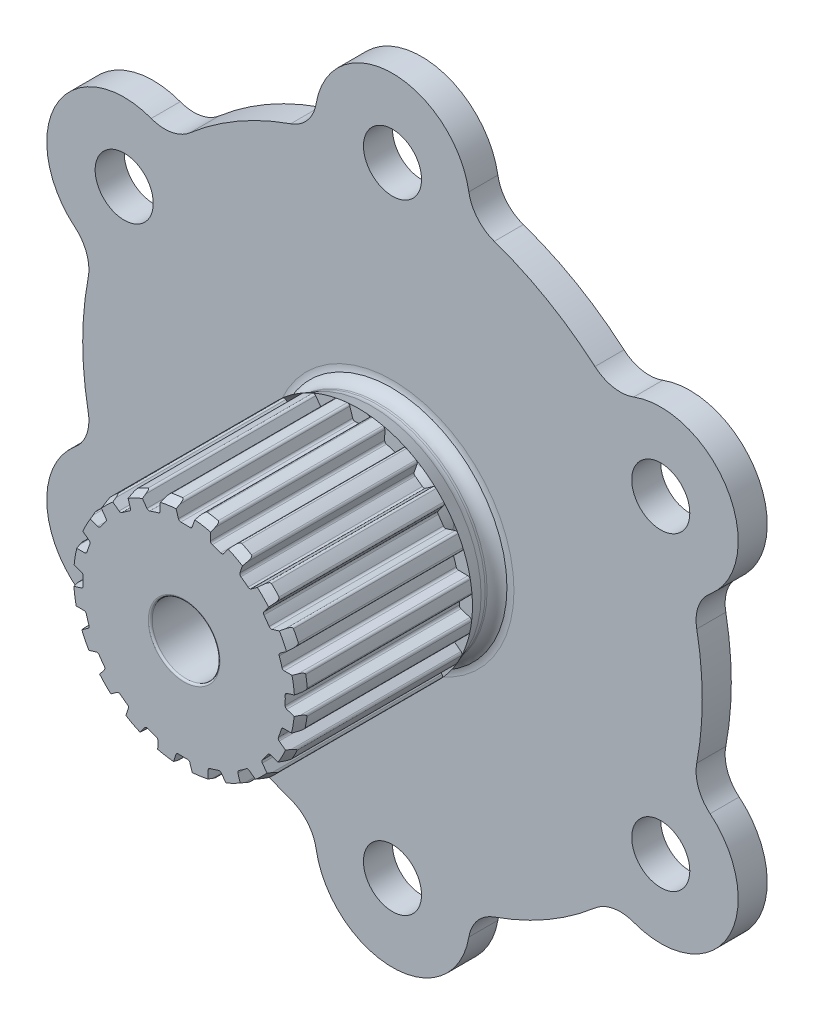
SolidWorks part; units mm, degrees
material "Alloy Steel (SS)"
ref_plane "Front Plane" through (0, 0, 0) normal (0, 0, 1) x (1, 0, 0)
ref_plane "Top Plane" through (0, 0, 0) normal (0, 1, 0) x (1, 0, 0)
ref_plane "Right Plane" through (0, 0, 0) normal (1, 0, 0) x (0, 0, -1)
sketch "Sketch1" plane through (0, 0, 0) normal (0, 0, 1) x (1, 0, 0)
  line L0 (0, -55) -> (0, 55) construction
  line L1 (0, 40) -> (0, 0) construction
  line L2 (0, 0) -> (0, -40) construction
  circle A1 centre (0, 32) radius 3
  circle A2 centre (0, 0) radius 41.3
  circle A3 centre (27.7128, 16) radius 3
  circle A4 centre (0, 0) radius 41.3
  circle A5 centre (27.7128, -16) radius 3
  circle A6 centre (0, 0) radius 41.3
  circle A7 centre (0, -32) radius 3
  circle A8 centre (0, 0) radius 41.3
  circle A9 centre (-27.7128, -16) radius 3
  circle A10 centre (0, 0) radius 41.3
  circle A11 centre (-27.7128, 16) radius 3
  arc A12 (-7.9373, 31) -> (-22.8782, 22.3739) centre (0, 0) ccw
  arc A13 (7.9373, 31) -> (-7.9373, 31) centre (0, 32) ccw
  arc A14 (30.8154, 8.6261) -> (22.8782, 22.3739) centre (27.7128, 16) ccw
  arc A15 (22.8782, -22.3739) -> (30.8154, -8.6261) centre (27.7128, -16) ccw
  arc A16 (-7.9373, -31) -> (7.9373, -31) centre (0, -32) ccw
  arc A17 (-30.8154, -8.6261) -> (-22.8782, -22.3739) centre (-27.7128, -16) ccw
  arc A18 (-22.8782, 22.3739) -> (-30.8154, 8.6261) centre (-27.7128, 16) ccw
  circle A19 centre (0, 32) radius 8 construction
  arc A20 (-22.8782, -22.3739) -> (-7.9373, -31) centre (0, 0) ccw
  arc A21 (30.8154, -8.6261) -> (30.8154, 8.6261) centre (0, 0) ccw
  arc A22 (-30.8154, 8.6261) -> (-30.8154, -8.6261) centre (0, 0) ccw
  arc A23 (7.9373, -31) -> (22.8782, -22.3739) centre (0, 0) ccw
  arc A25 (22.8782, 22.3739) -> (7.9373, 31) centre (0, 0) ccw
  point P25 (0, 0)
  point P38 (0, 0)
  dimension "D1" = 32
  dimension "D5" = 6
  dimension "D6" = 64
  dimension "D3" = 5
  dimension "D2" = 6
  dimension "D4" = 6
extrude "Boss-Extrude1" add sketch "Sketch1" along normal blind 3 contours A11 A9 A7 A5 A3 A1 region at (0, 0, 0)
fillet "Fillet3" radius 4 12 edges at (22.8782, -22.3739, 1.5) (7.9373, -31, 1.5) (-7.9373, -31, 1.5) (-22.8782, -22.3739, 1.5) (-30.8154, -8.6261, 1.5) (-30.8154, 8.6261, 1.5) (-22.8782, 22.3739, 1.5) (-7.9373, 31, 1.5) (7.9373, 31, 1.5) (30.8154, -8.6261, 1.5) (30.8154, 8.6261, 1.5) (22.8782, 22.3739, 1.5)
sketch "Sketch13" plane through (0, 0, 0) normal (0, 0, -1) x (-1, 0, 0)
  circle A0 centre (0, 0) radius 23.95
  circle A1 centre (0, 0) radius 20.95
  dimension "D2" = 47.9
  dimension "D1" = 3
extrude "Boss-Extrude8" add sketch "Sketch13" along normal blind 4
chamfer "Chamfer4" distance 1 angle 45 1 edges at (-23.95, 0, -4)
sketch "Sketch22" plane through (0, 0, 0) normal (1, 0, 0) x (0, 0, -1)
  line L0 (-3, 6.0027) -> (-3, -6.0027) construction
  line L4 (-6.5216, 0) -> (-6.5216, 11.78)
  line L5 (-3, 0) -> (-3, 12.0997)
  line L9 (-6.5216, 11.78) -> (-5.1121, 11.267)
  line L10 (-4.599, 11.1765) -> (-4.399, 11.1765)
  line L11 (-3.1, 11.9265) -> (-3, 12.0997)
  line L13 (-6.5216, 0) -> (-3, 0)
  arc A0 (-3.1, 11.9265) -> (-4.399, 11.1765) centre (-4.399, 12.6765) cw
  arc A1 (-4.599, 11.1765) -> (-5.1121, 11.267) centre (-4.599, 12.6765) cw
  point P0 (-3, 0)
  dimension "D3" = 1.5
  dimension "D1" = 160
  dimension "D2" = 120
  dimension "D4" = 0.2
  dimension "D5" = 1.5
  dimension "D6" = 11.78
  dimension "D7" = 0.2
revolve "Revolve1" add sketch "Sketch22" angle 360 about L13 region at (0, 5.7141, 4.7627)
sketch "Sketch23" plane through (0, 0, 6.5216) normal (0, 0, 1) x (1, 0, 0)
  line L80 (1.152, 11.5221) -> (0.841, 10.6016)
  line L81 (2.7177, 10.2818) -> (2.7291, 11.2534)
  line L82 (4.6562, 10.6022) -> (4.0759, 9.8228)
  line L83 (5.7619, 8.9387) -> (6.073, 9.8593)
  line L84 (7.7045, 8.6444) -> (6.9118, 8.0825)
  line L85 (8.2421, 6.7207) -> (8.8224, 7.5001)
  line L86 (9.9987, 5.8405) -> (9.0712, 5.5511)
  line L87 (9.9156, 3.8448) -> (10.7083, 4.4067)
  line L88 (11.3142, 2.4649) -> (10.3426, 2.4762)
  line L89 (10.6184, 0.5926) -> (11.5459, 0.882)
  line L90 (11.5221, -1.152) -> (10.6016, -0.841)
  line L91 (10.2818, -2.7177) -> (11.2534, -2.7291)
  line L92 (10.6022, -4.6562) -> (9.8228, -4.0759)
  line L93 (8.9387, -5.7619) -> (9.8593, -6.073)
  line L94 (8.6444, -7.7045) -> (8.0825, -6.9118)
  line L95 (6.7207, -8.2421) -> (7.5001, -8.8224)
  line L96 (5.8405, -9.9987) -> (5.5511, -9.0712)
  line L97 (3.8448, -9.9156) -> (4.4067, -10.7083)
  line L98 (2.4649, -11.3142) -> (2.4762, -10.3426)
  line L99 (0.5926, -10.6184) -> (0.882, -11.5459)
  line L100 (-1.152, -11.5221) -> (-0.841, -10.6016)
  line L101 (-2.7177, -10.2818) -> (-2.7291, -11.2534)
  line L102 (-4.6562, -10.6022) -> (-4.0759, -9.8228)
  line L103 (-5.7619, -8.9387) -> (-6.073, -9.8593)
  line L104 (-7.7045, -8.6444) -> (-6.9118, -8.0825)
  line L105 (-8.2421, -6.7207) -> (-8.8224, -7.5001)
  line L106 (-9.9987, -5.8405) -> (-9.0712, -5.5511)
  line L107 (-9.9156, -3.8448) -> (-10.7083, -4.4067)
  line L108 (-11.3142, -2.4649) -> (-10.3426, -2.4762)
  line L109 (-10.6184, -0.5926) -> (-11.5459, -0.882)
  line L110 (-11.5221, 1.152) -> (-10.6016, 0.841)
  line L111 (-10.2818, 2.7177) -> (-11.2534, 2.7291)
  line L112 (-10.6022, 4.6562) -> (-9.8228, 4.0759)
  line L113 (-8.9387, 5.7619) -> (-9.8593, 6.073)
  line L114 (-8.6444, 7.7045) -> (-8.0825, 6.9118)
  line L115 (-6.7207, 8.2421) -> (-7.5001, 8.8224)
  line L116 (-5.8405, 9.9987) -> (-5.5511, 9.0712)
  line L117 (-3.8448, 9.9156) -> (-4.4067, 10.7083)
  line L118 (-2.4649, 11.3142) -> (-2.4762, 10.3426)
  line L119 (-0.5926, 10.6184) -> (-0.882, 11.5459)
  arc A240 (1.4234, 11.6929) -> (1.152, 11.5221) centre (1.3927, 11.4408) ccw
  arc A241 (2.5296, 11.5044) -> (1.4234, 11.6929) centre (0, 0) ccw
  arc A242 (2.7291, 11.2534) -> (2.5296, 11.5044) centre (2.4751, 11.2563) ccw
  arc A243 (2.7177, 10.2818) -> (2.9011, 10.0348) centre (2.9717, 10.2788) ccw
  arc A244 (3.7802, 9.7377) -> (2.9011, 10.0348) centre (0, 0) ccw
  arc A245 (3.7802, 9.7377) -> (4.0759, 9.8228) centre (3.8722, 9.9745) ccw
  arc A246 (4.967, 10.6808) -> (4.6562, 10.6022) centre (4.8599, 10.4505) ccw
  arc A247 (5.9609, 10.1597) -> (4.967, 10.6808) centre (0, 0) ccw
  arc A248 (6.073, 9.8593) -> (5.9609, 10.1597) centre (5.8323, 9.9406) ccw
  arc A249 (5.7619, 8.9387) -> (5.8601, 8.6472) centre (6.0026, 8.8574) ccw
  arc A250 (6.6043, 8.093) -> (5.8601, 8.6472) centre (0, 0) ccw
  arc A251 (6.6043, 8.093) -> (6.9118, 8.0825) centre (6.7649, 8.2898) ccw
  arc A252 (8.0245, 8.6232) -> (7.7045, 8.6444) centre (7.8514, 8.4372) ccw
  arc A253 (8.8086, 7.8204) -> (8.0245, 8.6232) centre (0, 0) ccw
  arc A254 (8.8224, 7.5001) -> (8.8086, 7.8204) centre (8.6187, 7.6518) ccw
  arc A255 (8.2421, 6.7207) -> (8.2454, 6.4131) centre (8.4459, 6.569) ccw
  arc A256 (8.782, 5.656) -> (8.2454, 6.4131) centre (0, 0) ccw
  arc A257 (8.782, 5.656) -> (9.0712, 5.5511) centre (8.9955, 5.7936) ccw
  arc A258 (10.2964, 5.7214) -> (9.9987, 5.8405) centre (10.0744, 5.598) ccw
  arc A259 (10.7942, 4.7156) -> (10.2964, 5.7214) centre (0, 0) ccw
  arc A260 (10.7083, 4.4067) -> (10.7942, 4.7156) centre (10.5614, 4.6139) ccw
  arc A261 (9.9156, 3.8448) -> (9.8236, 3.5512) centre (10.0624, 3.6376) ccw
  arc A262 (10.1, 2.6654) -> (9.8236, 3.5512) centre (0, 0) ccw
  arc A263 (10.1, 2.6654) -> (10.3426, 2.4762) centre (10.3456, 2.7302) ccw
  arc A264 (11.5605, 2.2596) -> (11.3142, 2.4649) centre (11.3112, 2.2109) ccw
  arc A265 (11.7231, 1.1492) -> (11.5605, 2.2596) centre (0, 0) ccw
  arc A266 (11.5459, 0.882) -> (11.7231, 1.1492) centre (11.4703, 1.1245) ccw
  arc A267 (10.6184, 0.5926) -> (10.4402, 0.3418) centre (10.694, 0.3501) ccw
  arc A268 (10.4293, -0.5861) -> (10.4402, 0.3418) centre (0, 0) ccw
  arc A269 (10.4293, -0.5861) -> (10.6016, -0.841) centre (10.6829, -0.6003) ccw
  arc A270 (11.6929, -1.4234) -> (11.5221, -1.152) centre (11.4408, -1.3927) ccw
  arc A271 (11.5044, -2.5296) -> (11.6929, -1.4234) centre (0, 0) ccw
  arc A272 (11.2534, -2.7291) -> (11.5044, -2.5296) centre (11.2563, -2.4751) ccw
  arc A273 (10.2818, -2.7177) -> (10.0348, -2.9011) centre (10.2788, -2.9717) ccw
  arc A274 (9.7377, -3.7802) -> (10.0348, -2.9011) centre (0, 0) ccw
  arc A275 (9.7377, -3.7802) -> (9.8228, -4.0759) centre (9.9745, -3.8722) ccw
  arc A276 (10.6808, -4.967) -> (10.6022, -4.6562) centre (10.4505, -4.8599) ccw
  arc A277 (10.1597, -5.9609) -> (10.6808, -4.967) centre (0, 0) ccw
  arc A278 (9.8593, -6.073) -> (10.1597, -5.9609) centre (9.9406, -5.8323) ccw
  arc A279 (8.9387, -5.7619) -> (8.6472, -5.8601) centre (8.8574, -6.0026) ccw
  arc A280 (8.093, -6.6043) -> (8.6472, -5.8601) centre (0, 0) ccw
  arc A281 (8.093, -6.6043) -> (8.0825, -6.9118) centre (8.2898, -6.7649) ccw
  arc A282 (8.6232, -8.0245) -> (8.6444, -7.7045) centre (8.4372, -7.8514) ccw
  arc A283 (7.8204, -8.8086) -> (8.6232, -8.0245) centre (0, 0) ccw
  arc A284 (7.5001, -8.8224) -> (7.8204, -8.8086) centre (7.6518, -8.6187) ccw
  arc A285 (6.7207, -8.2421) -> (6.4131, -8.2454) centre (6.569, -8.4459) ccw
  arc A286 (5.656, -8.782) -> (6.4131, -8.2454) centre (0, 0) ccw
  arc A287 (5.656, -8.782) -> (5.5511, -9.0712) centre (5.7936, -8.9955) ccw
  arc A288 (5.7214, -10.2964) -> (5.8405, -9.9987) centre (5.598, -10.0744) ccw
  arc A289 (4.7156, -10.7942) -> (5.7214, -10.2964) centre (0, 0) ccw
  arc A290 (4.4067, -10.7083) -> (4.7156, -10.7942) centre (4.6139, -10.5614) ccw
  arc A291 (3.8448, -9.9156) -> (3.5512, -9.8236) centre (3.6376, -10.0624) ccw
  arc A292 (2.6654, -10.1) -> (3.5512, -9.8236) centre (0, 0) ccw
  arc A293 (2.6654, -10.1) -> (2.4762, -10.3426) centre (2.7302, -10.3456) ccw
  arc A294 (2.2596, -11.5605) -> (2.4649, -11.3142) centre (2.2109, -11.3112) ccw
  arc A295 (1.1492, -11.7231) -> (2.2596, -11.5605) centre (0, 0) ccw
  arc A296 (0.882, -11.5459) -> (1.1492, -11.7231) centre (1.1245, -11.4703) ccw
  arc A297 (0.5926, -10.6184) -> (0.3418, -10.4402) centre (0.3501, -10.694) ccw
  arc A298 (-0.5861, -10.4293) -> (0.3418, -10.4402) centre (0, 0) ccw
  arc A299 (-0.5861, -10.4293) -> (-0.841, -10.6016) centre (-0.6003, -10.6829) ccw
  arc A300 (-1.4234, -11.6929) -> (-1.152, -11.5221) centre (-1.3927, -11.4408) ccw
  arc A301 (-2.5296, -11.5044) -> (-1.4234, -11.6929) centre (0, 0) ccw
  arc A302 (-2.7291, -11.2534) -> (-2.5296, -11.5044) centre (-2.4751, -11.2563) ccw
  arc A303 (-2.7177, -10.2818) -> (-2.9011, -10.0348) centre (-2.9717, -10.2788) ccw
  arc A304 (-3.7802, -9.7377) -> (-2.9011, -10.0348) centre (0, 0) ccw
  arc A305 (-3.7802, -9.7377) -> (-4.0759, -9.8228) centre (-3.8722, -9.9745) ccw
  arc A306 (-4.967, -10.6808) -> (-4.6562, -10.6022) centre (-4.8599, -10.4505) ccw
  arc A307 (-5.9609, -10.1597) -> (-4.967, -10.6808) centre (0, 0) ccw
  arc A308 (-6.073, -9.8593) -> (-5.9609, -10.1597) centre (-5.8323, -9.9406) ccw
  arc A309 (-5.7619, -8.9387) -> (-5.8601, -8.6472) centre (-6.0026, -8.8574) ccw
  arc A310 (-6.6043, -8.093) -> (-5.8601, -8.6472) centre (0, 0) ccw
  arc A311 (-6.6043, -8.093) -> (-6.9118, -8.0825) centre (-6.7649, -8.2898) ccw
  arc A312 (-8.0245, -8.6232) -> (-7.7045, -8.6444) centre (-7.8514, -8.4372) ccw
  arc A313 (-8.8086, -7.8204) -> (-8.0245, -8.6232) centre (0, 0) ccw
  arc A314 (-8.8224, -7.5001) -> (-8.8086, -7.8204) centre (-8.6187, -7.6518) ccw
  arc A315 (-8.2421, -6.7207) -> (-8.2454, -6.4131) centre (-8.4459, -6.569) ccw
  arc A316 (-8.782, -5.656) -> (-8.2454, -6.4131) centre (0, 0) ccw
  arc A317 (-8.782, -5.656) -> (-9.0712, -5.5511) centre (-8.9955, -5.7936) ccw
  arc A318 (-10.2964, -5.7214) -> (-9.9987, -5.8405) centre (-10.0744, -5.598) ccw
  arc A319 (-10.7942, -4.7156) -> (-10.2964, -5.7214) centre (0, 0) ccw
  arc A320 (-10.7083, -4.4067) -> (-10.7942, -4.7156) centre (-10.5614, -4.6139) ccw
  arc A321 (-9.9156, -3.8448) -> (-9.8236, -3.5512) centre (-10.0624, -3.6376) ccw
  arc A322 (-10.1, -2.6654) -> (-9.8236, -3.5512) centre (0, 0) ccw
  arc A323 (-10.1, -2.6654) -> (-10.3426, -2.4762) centre (-10.3456, -2.7302) ccw
  arc A324 (-11.5605, -2.2596) -> (-11.3142, -2.4649) centre (-11.3112, -2.2109) ccw
  arc A325 (-11.7231, -1.1492) -> (-11.5605, -2.2596) centre (0, 0) ccw
  arc A326 (-11.5459, -0.882) -> (-11.7231, -1.1492) centre (-11.4703, -1.1245) ccw
  arc A327 (-10.6184, -0.5926) -> (-10.4402, -0.3418) centre (-10.694, -0.3501) ccw
  arc A328 (-10.4293, 0.5861) -> (-10.4402, -0.3418) centre (0, 0) ccw
  arc A329 (-10.4293, 0.5861) -> (-10.6016, 0.841) centre (-10.6829, 0.6003) ccw
  arc A330 (-11.6929, 1.4234) -> (-11.5221, 1.152) centre (-11.4408, 1.3927) ccw
  arc A331 (-11.5044, 2.5296) -> (-11.6929, 1.4234) centre (0, 0) ccw
  arc A332 (-11.2534, 2.7291) -> (-11.5044, 2.5296) centre (-11.2563, 2.4751) ccw
  arc A333 (-10.2818, 2.7177) -> (-10.0348, 2.9011) centre (-10.2788, 2.9717) ccw
  arc A334 (-9.7377, 3.7802) -> (-10.0348, 2.9011) centre (0, 0) ccw
  arc A335 (-9.7377, 3.7802) -> (-9.8228, 4.0759) centre (-9.9745, 3.8722) ccw
  arc A336 (-10.6808, 4.967) -> (-10.6022, 4.6562) centre (-10.4505, 4.8599) ccw
  arc A337 (-10.1597, 5.9609) -> (-10.6808, 4.967) centre (0, 0) ccw
  arc A338 (-9.8593, 6.073) -> (-10.1597, 5.9609) centre (-9.9406, 5.8323) ccw
  arc A339 (-8.9387, 5.7619) -> (-8.6472, 5.8601) centre (-8.8574, 6.0026) ccw
  arc A340 (-8.093, 6.6043) -> (-8.6472, 5.8601) centre (0, 0) ccw
  arc A341 (-8.093, 6.6043) -> (-8.0825, 6.9118) centre (-8.2898, 6.7649) ccw
  arc A342 (-8.6232, 8.0245) -> (-8.6444, 7.7045) centre (-8.4372, 7.8514) ccw
  arc A343 (-7.8204, 8.8086) -> (-8.6232, 8.0245) centre (0, 0) ccw
  arc A344 (-7.5001, 8.8224) -> (-7.8204, 8.8086) centre (-7.6518, 8.6187) ccw
  arc A345 (-6.7207, 8.2421) -> (-6.4131, 8.2454) centre (-6.569, 8.4459) ccw
  arc A346 (-5.656, 8.782) -> (-6.4131, 8.2454) centre (0, 0) ccw
  arc A347 (-5.656, 8.782) -> (-5.5511, 9.0712) centre (-5.7936, 8.9955) ccw
  arc A348 (-5.7214, 10.2964) -> (-5.8405, 9.9987) centre (-5.598, 10.0744) ccw
  arc A349 (-4.7156, 10.7942) -> (-5.7214, 10.2964) centre (0, 0) ccw
  arc A350 (-4.4067, 10.7083) -> (-4.7156, 10.7942) centre (-4.6139, 10.5614) ccw
  arc A351 (-3.8448, 9.9156) -> (-3.5512, 9.8236) centre (-3.6376, 10.0624) ccw
  arc A352 (-2.6654, 10.1) -> (-3.5512, 9.8236) centre (0, 0) ccw
  arc A353 (-2.6654, 10.1) -> (-2.4762, 10.3426) centre (-2.7302, 10.3456) ccw
  arc A354 (-2.2596, 11.5605) -> (-2.4649, 11.3142) centre (-2.2109, 11.3112) ccw
  arc A355 (-1.1492, 11.7231) -> (-2.2596, 11.5605) centre (0, 0) ccw
  arc A356 (-0.882, 11.5459) -> (-1.1492, 11.7231) centre (-1.1245, 11.4703) ccw
  arc A357 (-0.5926, 10.6184) -> (-0.3418, 10.4402) centre (-0.3501, 10.694) ccw
  arc A358 (0.5861, 10.4293) -> (-0.3418, 10.4402) centre (0, 0) ccw
  arc A359 (0.5861, 10.4293) -> (0.841, 10.6016) centre (0.6003, 10.6829) ccw
extrude "Boss-Extrude9" add sketch "Sketch23" along normal blind 18
sketch "Sketch24" plane through (0, 0, 0) normal (0, 1, 0) x (1, 0, 0)
  line L0 (-23.45, 0.5) -> (-23.45, -0.5)
  line L2 (-23.45, -0.5) -> (-24.45, -0.5)
  line L4 (-23.45, 0.5) -> (-24.45, 0.5)
  line L5 (-24.45, -0.5) -> (-24.45, 0.5)
  line L6 (-23.95, 3) -> (-23.95, 0) construction
  line L7 (-20.9145, 0) -> (-24.9235, 0) construction
  line L8 (0, 0) -> (0, 7.2289) construction
  line L9 (7.8881, 0) -> (-7.8881, 0) construction
  point P0 (0, 0)
  point P2 (-23.95, 0.5)
  dimension "D1" = 0
  dimension "D2" = 1
  dimension "D3" = 1
  dimension "D4" = 0.5
revolve "Cut-Revolve1" cut sketch "Sketch24" angle 360 about L8 region at (-23.95, 0, 0)
fillet "Fillet5" radius 0.5 2 edges at (23.95, 0, -0.5) (24.45, 0, 0)
fillet "Fillet6" radius 0.5 3 edges at (23.45, 0, 0.5) (24.45, 0, 0.5) (23.45, 0, -0.5)
fillet "Fillet7" radius 2 1 edges at (12.0997, 0, 3)
sketch "Sketch25" plane through (0, 0, 24.5216) normal (0, 0, 1) x (1, 0, 0)
  circle A0 centre (0, 0) radius 3.5
extrude "Cut-Extrude1" cut sketch "Sketch25" against normal through all
fillet "Fillet8" radius 0.2 2 edges at (3.5, 0, 24.5216) (3.5, 0, 0)
ref_plane "Plane1" through (0, 0, 0) normal (-0.9895, -0.1449, 0) x (0, 0, 1)
sketch "Sketch27" plane through (0, 0, 0) normal (-0.9895, -0.1449, 0) x (0, 0, 1)
  line L1 (23.5216, 11.7799) -> (24.5216, 11.7799)
  line L3 (25.6465, 0) -> (27.067, 0) construction
  line L4 (24.5216, 11.4159) -> (24.5216, 11.7799)
  line L5 (24.5216, 11.4159) -> (23.5216, 11.7799)
  line L7 (24.5216, 11.7659) -> (6.5216, 11.7659) construction
  line L8 (24.5216, 11.5519) -> (24.5216, 11.7659) construction
  dimension "D1" = 1
  dimension "D2" = 0.014
  dimension "D3" = 70
revolve "Cut-Revolve4" cut sketch "Sketch27" angle 360 about L3
fillet "Fillet9" radius 1 1 edges at (-20.95, 0, 0)
